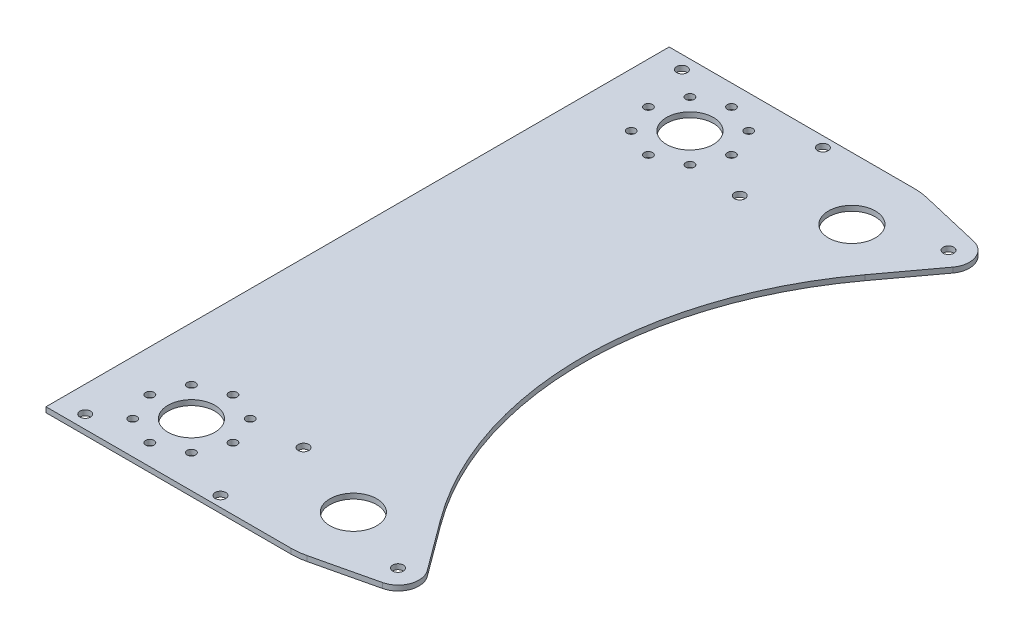
SolidWorks part; units mm, degrees
material "6061-T6 (SS)"
ref_plane "Front Plane" through (0, 0, 0) normal (0, 0, 1) x (1, 0, 0)
ref_plane "Top Plane" through (0, 0, 0) normal (0, 1, 0) x (1, 0, 0)
ref_plane "Right Plane" through (0, 0, 0) normal (1, 0, 0) x (0, 0, -1)
sketch "Sketch1" plane through (0, 0, 0) normal (0, 1, 0) x (1, 0, 0)
  line L1 (120.65, -190.5) -> (-120.65, -190.5)
  line L2 (120.65, -190.5) -> (120.65, 190.5)
  line L3 (120.65, 190.5) -> (-120.65, 190.5)
  line L4 (-120.65, -190.5) -> (-120.65, 190.5)
  line L5 (120.65, -190.5) -> (-120.65, 190.5) construction
  line L6 (120.65, 190.5) -> (-120.65, -190.5) construction
  point P0 (0, 0)
  dimension "D1" = 241.3
  dimension "D2" = 381
extrude "Boss-Extrude1" add sketch "Sketch1" along normal blind 3.175
sketch "Sketch6" plane through (0, 3.175, 0) normal (0, 1, 0) x (1, 0, 0)
  line L1 (-69.85, 152.4) -> (0, 0) construction
  line L2 (0, 0) -> (-69.85, -152.4) construction
  line L5 (-120.65, 190.5) -> (-120.65, -190.5) construction
  circle A0 centre (-69.85, -152.4) radius 38.1 construction
  circle A1 centre (-69.85, 152.4) radius 38.1 construction
  circle A2 centre (29.1592, -152.4) radius 38.1 construction
  circle A3 centre (29.1592, 152.4) radius 38.1 construction
  dimension "D1" = 76.2
  dimension "D5" = 228.6
  dimension "D3" = 99.0092
  dimension "D4" = 50.8
sketch "Sketch7" plane through (0, 3.175, 0) normal (0, 1, 0) x (1, 0, 0)
  circle A0 centre (29.1592, -152.4) radius 14.3129
  circle A1 centre (29.1592, 152.4) radius 14.3129
  circle A2 centre (-69.85, 152.4) radius 14.3129
  circle A3 centre (-69.85, -152.4) radius 14.3129
  circle A4 centre (-95.25, 152.4) radius 2.5527
  circle A5 centre (-69.85, 152.4) radius 25.4 construction
  circle A6 centre (-87.8105, 170.3605) radius 2.5527
  circle A7 centre (-69.85, 177.8) radius 2.5527
  circle A8 centre (-51.8895, 170.3605) radius 2.5527
  circle A9 centre (-69.85, -152.4) radius 25.4 construction
  circle A10 centre (-69.85, -127) radius 2.5527
  circle A11 centre (-51.8895, -134.4395) radius 2.5527
  circle A12 centre (-44.45, -152.4) radius 2.5527
  circle A13 centre (-51.8895, -170.3605) radius 2.5527
  circle A14 centre (-44.45, 152.4) radius 2.5527
  circle A15 centre (-51.8895, 134.4395) radius 2.5527
  circle A16 centre (-69.85, 127) radius 2.5527
  circle A17 centre (-87.8105, 134.4395) radius 2.5527
  circle A18 centre (-69.85, -177.8) radius 2.5527
  circle A19 centre (-87.8105, -170.3605) radius 2.5527
  circle A20 centre (-95.25, -152.4) radius 2.5527
  circle A21 centre (-87.8105, -134.4395) radius 2.5527
  point P24 (-69.85, 152.4)
  point P34 (-69.85, -152.4)
  point P40 (0, 0)
  point P49 (0, 0)
  dimension "D1" = 28.6258
  dimension "D2" = 28.6258
  dimension "D3" = 5.1054
  dimension "D5" = 50.8
  dimension "D4" = 8
  dimension "D6" = 8
extrude "Axle Holes" cut sketch "Sketch7" against normal through all
sketch "Sketch10" plane through (0, 3.175, 0) normal (0, 1, 0) x (1, 0, 0)
  line L0 (0, 0) -> (57.9248, 0) construction
  circle A0 centre (-104.775, -182.3949) radius 3.2385
  circle A1 centre (-20.3454, -184.15) radius 3.2385
  circle A2 centre (-20.3454, -133.35) radius 2.5527 construction
  circle A3 centre (-20.3454, -133.35) radius 3.2385
  circle A4 centre (72.373, -168.275) radius 3.2385
  circle A10 centre (-104.775, -182.3949) radius 2.5527 construction
  circle A11 centre (-20.3454, -184.15) radius 2.5527 construction
  circle A12 centre (72.373, -168.275) radius 2.5527 construction
  circle A13 centre (-20.3454, -133.35) radius 2.5527 construction
  circle A14 centre (-104.775, -182.3949) radius 2.5527 construction
  circle A15 centre (-20.3454, -184.15) radius 2.5527 construction
  circle A16 centre (72.373, -168.275) radius 2.5527 construction
  circle A17 centre (72.373, 168.275) radius 3.2385
  circle A18 centre (-20.3454, 184.15) radius 3.2385
  circle A19 centre (-20.3454, 133.35) radius 3.2385
  circle A20 centre (-104.775, 182.3949) radius 3.2385
  dimension "D1" = 6.477
extrude "Cut-Extrude5" cut sketch "Sketch10" against normal through all
sketch "Sketch8" plane through (0, 3.175, 0) normal (0, 1, 0) x (1, 0, 0)
  line L0 (59.8106, -129.7704) -> (82.6413, -160.6941)
  line L1 (37.8719, -189.4904) -> (75.2918, -180.7003)
  line L5 (0, 0) -> (-35.0112, 0) construction
  line L6 (59.8106, 129.7704) -> (82.6413, 160.6941)
  line L7 (37.8719, 189.4904) -> (75.2918, 180.7003)
  circle A4 centre (29.1592, -152.4) radius 38.1 construction
  circle A5 centre (72.373, -168.275) radius 12.7635 construction
  arc A7 (75.2918, -180.7003) -> (82.6413, -160.6941) centre (72.373, -168.275) ccw
  arc A8 (59.8106, -129.7704) -> (59.8106, 129.7704) centre (235.5823, 0) cw
  circle A9 centre (72.373, -168.275) radius 3.2385 construction
  arc A10 (75.2918, 180.7003) -> (82.6413, 160.6941) centre (72.373, 168.275) cw
  arc A11 (37.8719, -189.4904) -> (29.1592, -190.5) centre (29.1592, -152.4) cw
  arc A12 (37.8719, 189.4904) -> (29.1592, 190.5) centre (29.1592, 152.4) ccw
  dimension "D2" = 9.525
  dimension "D1" = 76.2
extrude "Cut-Extrude4" cut sketch "Sketch8" against normal through all flip side to cut
